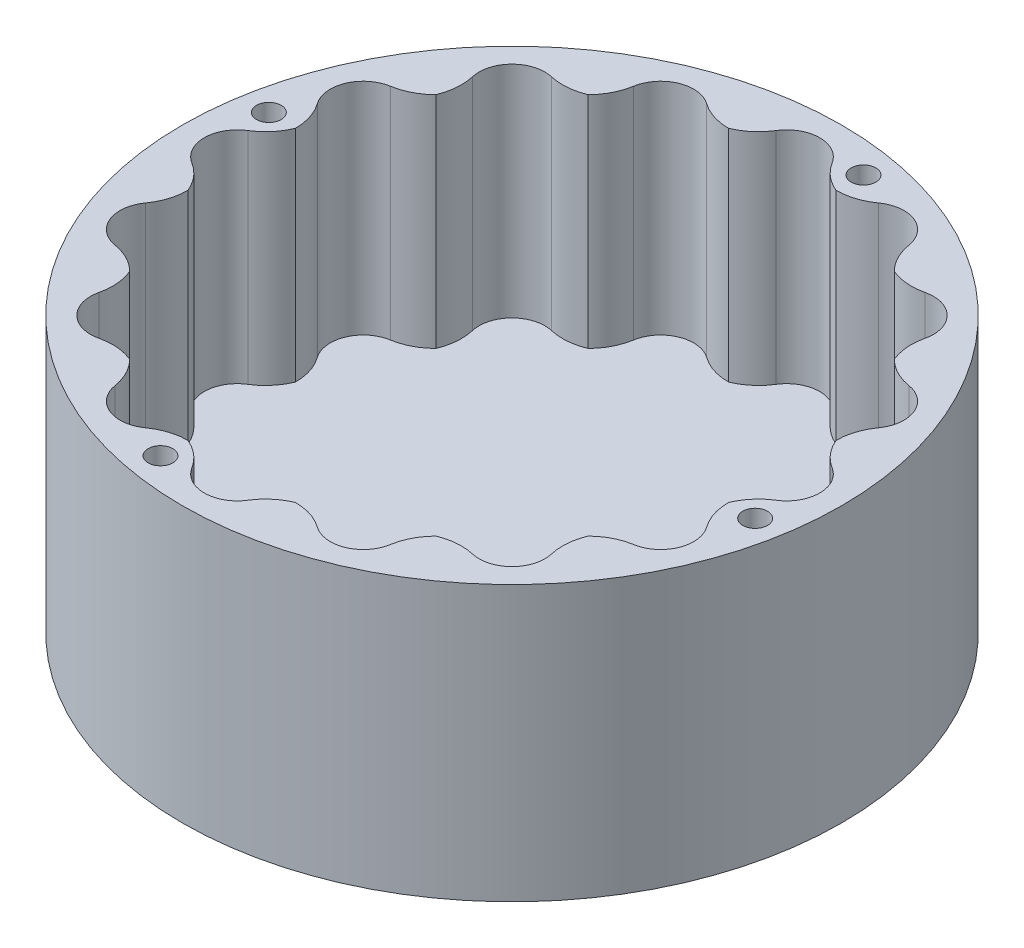
SolidWorks part; units mm, degrees
ref_plane "Front Plane" through (0, 0, 0) normal (0, 0, 1) x (1, 0, 0)
ref_plane "Top Plane" through (0, 0, 0) normal (0, 1, 0) x (1, 0, 0)
ref_plane "Right Plane" through (0, 0, 0) normal (1, 0, 0) x (0, 0, -1)
sketch "Sketch1" plane through (0, 0, 0) normal (0, 1, 0) x (1, 0, 0)
  arc A0 (-50.0283, 13.4631) -> (-51.515, 5.9892) centre (-1.875, 0) ccw
  arc A1 (4.1142, 49.64) -> (-7.8642, 49.64) centre (-1.875, 50) ccw
  arc A2 (-16.6515, 42.0695) -> (-16.6233, 42.0995) centre (-21.0092, 46.194) ccw
  arc A3 (-32.7408, 39.3358) -> (-41.2108, 30.8658) centre (-37.2303, 35.3553) ccw
  arc A4 (-45.4444, 24.5297) -> (-50.0283, 13.4631) centre (-48.069, 19.1342) ccw
  arc A5 (-51.515, 5.9892) -> (-51.515, -5.9892) centre (-51.875, 0) ccw
  arc A6 (-50.0283, -13.4631) -> (-45.4444, -24.5297) centre (-48.069, -19.1342) ccw
  arc A7 (-41.2108, -30.8658) -> (-32.7408, -39.3358) centre (-37.2303, -35.3553) ccw
  arc A8 (-26.4047, -43.5694) -> (-15.3381, -48.1533) centre (-21.0092, -46.194) ccw
  arc A9 (-7.8642, -49.64) -> (4.1142, -49.64) centre (-1.875, -50) ccw
  arc A10 (11.5881, -48.1533) -> (22.6547, -43.5694) centre (17.2592, -46.194) ccw
  arc A11 (28.9908, -39.3358) -> (37.4608, -30.8658) centre (33.4803, -35.3553) ccw
  arc A12 (40.4731, -14.5288) -> (40.4074, -14.5845) centre (44.319, -19.1342) ccw
  arc A13 (47.765, -5.9892) -> (47.765, 5.9892) centre (48.125, 0) ccw
  arc A14 (40.4074, 14.5845) -> (40.4731, 14.5288) centre (44.319, 19.1342) ccw
  arc A15 (37.4608, 30.8658) -> (28.9908, 39.3358) centre (33.4803, 35.3553) ccw
  arc A16 (22.6547, 43.5694) -> (11.5881, 48.1533) centre (17.2592, 46.194) ccw
  circle A17 centre (-1.875, 0) radius 60
  arc A18 (-41.2108, 30.8658) -> (-45.4444, 24.5297) centre (-1.875, 0) ccw
  arc A19 (-26.4047, 43.5694) -> (-32.7408, 39.3358) centre (-1.875, 0) ccw
  arc A20 (-15.3381, 48.1533) -> (-26.4047, 43.5694) centre (-21.0092, 46.194) ccw
  arc A21 (-7.8642, 49.64) -> (-15.3381, 48.1533) centre (-1.875, 0) ccw
  arc A22 (11.5881, 48.1533) -> (4.1142, 49.64) centre (-1.875, 0) ccw
  arc A23 (28.9908, 39.3358) -> (22.6547, 43.5694) centre (-1.875, 0) ccw
  arc A24 (41.6944, 24.5297) -> (37.4608, 30.8658) centre (-1.875, 0) ccw
  arc A25 (46.2783, 13.4631) -> (41.6944, 24.5297) centre (44.319, 19.1342) ccw
  arc A26 (46.2783, -13.4631) -> (47.765, -5.9892) centre (-1.875, 0) ccw
  arc A27 (41.6944, -24.5297) -> (46.2783, -13.4631) centre (44.319, -19.1342) ccw
  arc A28 (37.4608, -30.8658) -> (41.6944, -24.5297) centre (-1.875, 0) ccw
  arc A29 (-51.515, -5.9892) -> (-50.0283, -13.4631) centre (-1.875, 0) ccw
  arc A30 (-45.4444, -24.5297) -> (-41.2108, -30.8658) centre (-1.875, 0) ccw
  arc A31 (-32.7408, -39.3358) -> (-26.4047, -43.5694) centre (-1.875, 0) ccw
  arc A32 (-15.3381, -48.1533) -> (-7.8642, -49.64) centre (-1.875, 0) ccw
  arc A33 (-16.6233, -42.0995) -> (-16.6515, -42.0695) centre (-21.0092, -46.194) ccw
  arc A34 (4.1142, -49.64) -> (11.5881, -48.1533) centre (-1.875, 0) ccw
  arc A35 (22.6547, -43.5694) -> (28.9908, -39.3358) centre (-1.875, 0) ccw
  arc A36 (47.765, 5.9892) -> (46.2783, 13.4631) centre (-1.875, 0) ccw
  spline S0 degree 4 poles (44.0747, 11.4987) (44.2543, 11.2167) (44.5698, 10.6242) (44.9021, 9.6808) (45.0642, 8.3642) (44.9446, 7.1282) (44.593, 6.0249) (44.1211, 5.1947) (43.695, 4.5754) (43.3564, 4.0472) (43.0998, 3.6163) (42.8821, 3.198) (42.6994, 2.7973) (42.5503, 2.4153) (42.4301, 2.0557) (42.3415, 1.7357) (42.2778, 1.4587) (42.224, 1.1791) (42.1875, 0.9457) (42.1595, 0.7089) (42.1421, 0.4978) (42.1336, 0.3578) (42.1278, 0.2085) (42.1243, 0.037) (42.1247, -0.0678) (42.1293, -0.2634) (42.1379, -0.4367) (42.15, -0.5999) (42.1691, -0.7936) (42.1974, -1.0101) (42.2414, -1.2799) (42.3074, -1.6012) (42.4037, -1.9716) (42.5387, -2.3877) (42.6983, -2.7948) (42.8796, -3.1931) (43.1366, -3.6835) (43.482, -4.2594) (43.9287, -4.9065) (44.4091, -5.6745) (44.8007, -6.6105) (45.0295, -7.7093) (45.0295, -8.9484) (44.7352, -10.2696) (44.1902, -11.4212) (43.4619, -12.3657) (42.6206, -13.0778) (41.7593, -13.602) (40.7824, -14.2408) (39.77, -15.1062) (38.838, -16.2841) (38.1405, -17.7977) (37.8498, -19.2831) (37.8586, -20.6377) (38.0279, -21.8199) (38.2279, -22.8394) (38.2788, -23.9779) (38.0615, -25.1966) (37.5489, -26.4121) (36.7247, -27.5436) (35.7476, -28.3911) (34.706, -28.96) (33.6586, -29.2738) (32.6702, -29.405) (31.5286, -29.5836) (30.2595, -29.9481) (28.9262, -30.6268) (27.659, -31.7106) (26.7717, -32.9447) (26.2118, -34.1914) (25.9145, -35.2243) (25.7304, -35.9895) (25.5039, -36.7438) (25.1586, -37.555) (24.5413, -38.4785) (23.5696, -39.3957) (22.3328, -40.1097) (21.0527, -40.4927) (19.9443, -40.5655) (19.0691, -40.4589) (18.3026, -40.2779) (17.5479, -40.0547) (16.5047, -39.7958) (15.1451, -39.6573) (13.6327, -39.8087) (12.0605, -40.3642) (10.8061, -41.1795) (9.8558, -42.0964) (9.1304, -42.9957) (8.5226, -43.7861) (7.7271, -44.5363) (6.7136, -45.1539) (5.4911, -45.5763) (4.0991, -45.7244) (2.7902, -45.5605) (1.6261, -45.1394) (0.6656, -44.526) (-0.1173, -43.8431) (-1.0565, -43.1053) (-2.2252, -42.4205) (-3.657, -41.9295) (-5.3166, -41.7767) (-6.8026, -41.9949) (-8.0583, -42.439) (-9.1, -42.9656) (-9.9846, -43.4494) (-11.0219, -43.8219) (-12.2041, -43.9805) (-13.4901, -43.8751) (-14.8122, -43.455) (-15.9301, -42.7928) (-16.8127, -41.9651) (-17.4446, -41.0507) (-17.8788, -40.1387) (-18.4163, -39.084) (-19.1877, -37.9587) (-20.2985, -36.882) (-21.7915, -36.02) (-23.2794, -35.5964) (-24.6396, -35.491) (-25.8217, -35.5529) (-26.8286, -35.6328) (-27.9365, -35.5428) (-29.0946, -35.1922) (-30.227, -34.5552) (-31.2519, -33.6204) (-31.9862, -32.5593) (-32.4399, -31.4562) (-32.636, -30.3717) (-32.6594, -29.3636) (-32.7241, -28.1982) (-32.9674, -26.8887) (-33.5214, -25.4926) (-34.4835, -24.1318) (-35.6246, -23.1374) (-36.8021, -22.4676) (-37.9106, -22.0232) (-38.8934, -21.6866) (-39.9049, -21.1614) (-40.8517, -20.3639) (-41.648, -19.3123) (-42.2158, -18.0327) (-42.4612, -16.7628) (-42.4331, -15.5762) (-42.1811, -14.5123) (-41.8006, -13.5907) (-41.3845, -12.5128) (-41.0655, -11.2314) (-40.9867, -9.7374) (-41.2916, -8.0981) (-41.8623, -6.8333) (-42.485, -5.9251) (-43.0125, -5.3085) (-43.3736, -4.9275) (-43.7476, -4.5595) (-44.1231, -4.193) (-44.4829, -3.8105) (-44.8105, -3.3997) (-45.0744, -2.9955) (-45.2825, -2.6081) (-45.444, -2.2456) (-45.5676, -1.9138) (-45.6577, -1.6174) (-45.7221, -1.3598) (-45.7672, -1.1433) (-45.7981, -0.9691) (-45.8239, -0.7941) (-45.8419, -0.6396) (-45.8542, -0.5087) (-45.8622, -0.3996) (-45.8674, -0.31) (-45.8722, -0.1929) (-45.8754, -0.0484) (-45.8754, 0.057) (-45.8707, 0.2539) (-45.8614, 0.4217) (-45.8475, 0.5867) (-45.8289, 0.7543) (-45.8057, 0.9209) (-45.7778, 1.0866) (-45.7208, 1.3751) (-45.6162, 1.7824) (-45.4517, 2.2512) (-45.2056, 2.7679) (-44.9364, 3.2145) (-44.6596, 3.5954) (-44.3529, 3.9526) (-44.0247, 4.2897) (-43.6878, 4.6178) (-43.3537, 4.9489) (-43.036, 5.2844) (-42.7388, 5.6275) (-42.4647, 5.9787) (-42.2147, 6.3375) (-41.9285, 6.8032) (-41.6301, 7.388) (-41.2988, 8.2445) (-41.0869, 9.2182) (-41.0245, 10.1783) (-41.079, 10.9169) (-41.1306, 11.2832) (-41.1623, 11.4653) knots 0 0 0 0 0 0.00752 0.015039 0.022311 0.029582 0.03522 0.040858 0.043677 0.046496 0.049315 0.052134 0.054265 0.056396 0.058526 0.060657 0.061722 0.062788 0.064918 0.065984 0.067049 0.067582 0.068115 0.06918 0.070492 0.071149 0.071805 0.073033 0.074262 0.07549 0.076719 0.079176 0.081633 0.084089 0.086546 0.089003 0.09146 0.096539 0.101618 0.106697 0.111776 0.11923 0.126684 0.134323 0.141963 0.147625 0.153288 0.15895 0.164612 0.173852 0.183092 0.192408 0.201724 0.207559 0.213395 0.219231 0.225067 0.233024 0.240981 0.24862 0.25626 0.261858 0.267455 0.273053 0.278651 0.287828 0.297005 0.30639 0.315776 0.321674 0.327572 0.330521 0.33347 0.339368 0.347323 0.355277 0.363232 0.371186 0.377084 0.380033 0.382982 0.38888 0.394778 0.404164 0.413549 0.422726 0.431904 0.437501 0.443099 0.448697 0.454294 0.461934 0.469574 0.477531 0.485487 0.491323 0.497159 0.502995 0.508831 0.518146 0.527462 0.536702 0.545942 0.551604 0.557267 0.562929 0.568591 0.576231 0.58387 0.591691 0.599511 0.605182 0.610853 0.616525 0.622196 0.631785 0.641374 0.650964 0.660553 0.666224 0.671895 0.677566 0.683238 0.691058 0.698878 0.706518 0.714157 0.71982 0.725482 0.731145 0.736807 0.746047 0.755287 0.764602 0.773918 0.779754 0.78559 0.791426 0.797261 0.805218 0.813175 0.820815 0.828454 0.834052 0.83965 0.845248 0.850845 0.860022 0.869199 0.878585 0.887971 0.89092 0.893869 0.896818 0.899767 0.902716 0.905665 0.908614 0.911563 0.913551 0.91554 0.917528 0.919517 0.920511 0.921506 0.9225 0.923494 0.924489 0.924986 0.925483 0.92598 0.926477 0.927472 0.928416 0.929361 0.930305 0.931249 0.932194 0.933138 0.934083 0.935027 0.938805 0.942583 0.945226 0.947869 0.950513 0.953156 0.955799 0.958442 0.961086 0.963729 0.966185 0.968641 0.971097 0.973554 0.978466 0.983378 0.991689 0.995845 1 1 1 1 1 construction
  spline S1 degree 4 poles (40.4731, -14.5288) (40.4566, -14.5426) (40.4402, -14.5565) (40.4237, -14.5705) (40.4074, -14.5845) knots 0.165033 0.165033 0.165033 0.165033 0.165033 0.165518 0.165518 0.165518 0.165518 0.165518
  spline S2 degree 4 poles (40.4731, 14.5288) (40.4566, 14.5426) (40.4402, 14.5565) (40.4237, 14.5705) (40.4074, 14.5845) knots 0.165033 0.165033 0.165033 0.165033 0.165033 0.165518 0.165518 0.165518 0.165518 0.165518
  spline S3 degree 4 poles (-16.6233, 42.0995) (-16.6304, 42.0921) (-16.6375, 42.0846) (-16.6445, 42.0771) (-16.6515, 42.0695) knots 0.600544 0.600544 0.600544 0.600544 0.600544 0.600775 0.600775 0.600775 0.600775 0.600775
  dimension "D1" = 16
extrude "Boss-Extrude1" add sketch "Sketch1" along normal blind 50 contours A17 | A26 A13 A36 A25 A24 A15 A23 A16 A22 A1 A21 A20 A19 A3 A18 A4 A0 A5 A29 A6 A30 A7 A31 A8 A32 A9 A34 A10 A35 A11 A28 A27
sketch "Sketch3" plane through (0, 0, 0) normal (0, 1, 0) x (1, 0, 0)
  circle A0 centre (-1.875, 0) radius 60
extrude "Boss-Extrude2" add sketch "Sketch3" along normal blind 10
fillet "Fillet1" radius 10 2 edges at (11.5881, 30, -48.1533) (4.1142, 30, -49.64)
fillet "Fillet2" radius 10 30 edges at (-50.0283, 30, -13.4631) (-51.515, 30, -5.9892) (-51.515, 30, 5.9892) (-50.0283, 30, 13.4631) (-45.4444, 30, 24.5297) (-41.2108, 30, 30.8658) (-32.7408, 30, 39.3358) (-26.4047, 30, 43.5694) (-15.3381, 30, 48.1533) (-7.8642, 30, 49.64) (-45.4444, 30, -24.5297) (-41.2108, 30, -30.8658) (-32.7408, 30, -39.3358) (-26.4047, 30, -43.5694) (-7.8642, 30, -49.64) (-15.3381, 30, -48.1533) (4.1142, 30, 49.64) (11.5881, 30, 48.1533) (22.6547, 30, 43.5694) (28.9908, 30, 39.3358) (37.4608, 30, 30.8658) (41.6944, 30, 24.5297) (46.2783, 30, 13.4631) (47.765, 30, 5.9892) (47.765, 30, -5.9892) (46.2783, 30, -13.4631) (41.6944, 30, -24.5297) (37.4608, 30, -30.8658) (28.9908, 30, -39.3358) (22.6547, 30, -43.5694)
sketch "Sketch5" plane through (0, 50, 0) normal (0, 1, 0) x (1, 0, 0)
  circle A0 centre (-11.7359, -54.1088) radius 2.25
  circle A3 centre (-55.9838, 9.8609) radius 2.25
  circle A4 centre (7.9859, 54.1088) radius 2.25
  circle A5 centre (52.2338, -9.8609) radius 2.25
  point P12 (-1.875, 0)
  dimension "D1" = 4
extrude "Cut-Extrude2" cut sketch "Sketch5" against normal blind 6.1 contours A4 | A3 | A0 | A5 region at (7.9859, 50, -54.1088)
